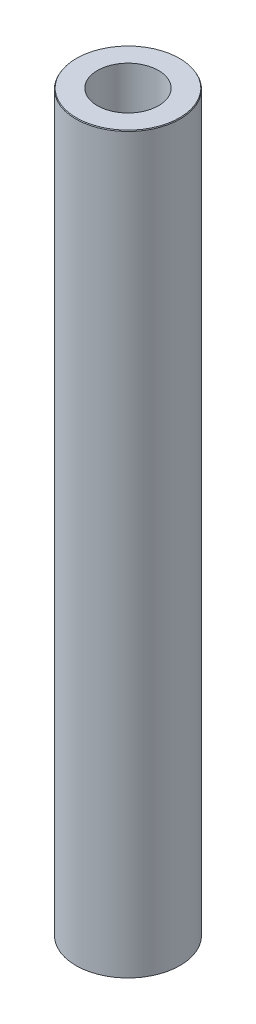
SolidWorks part; units mm, degrees
ref_plane "Front Plane" through (0, 0, 0) normal (0, 0, 1) x (1, 0, 0)
ref_plane "Top Plane" through (0, 0, 0) normal (0, 1, 0) x (1, 0, 0)
ref_plane "Right Plane" through (0, 0, 0) normal (1, 0, 0) x (0, 0, -1)
sketch "Sketch1" plane through (0, 0, 0) normal (0, 1, 0) x (1, 0, 0)
  circle A0 centre (0, 0) radius 42.5
  dimension "SHAFT_OD" = 85
extrude "Boss-Extrude1" add sketch "Sketch1" along normal blind 600
sketch "Sketch2" plane through (0, 0, 0) normal (0, 1, 0) x (1, 0, 0)
  circle A0 centre (0, 0) radius 24.9629
  dimension "BORE_D" = 49.9257
extrude "Cut-Extrude1" cut sketch "Sketch2" along normal through all
chamfer "Chamfer1" distance 0.687 angle 30 2 edges at (0, 600, 42.5) (0, 0, 42.5) first distance on face at (0, 600, 42.5) first distance on face at (0, 0, 24.9629)
